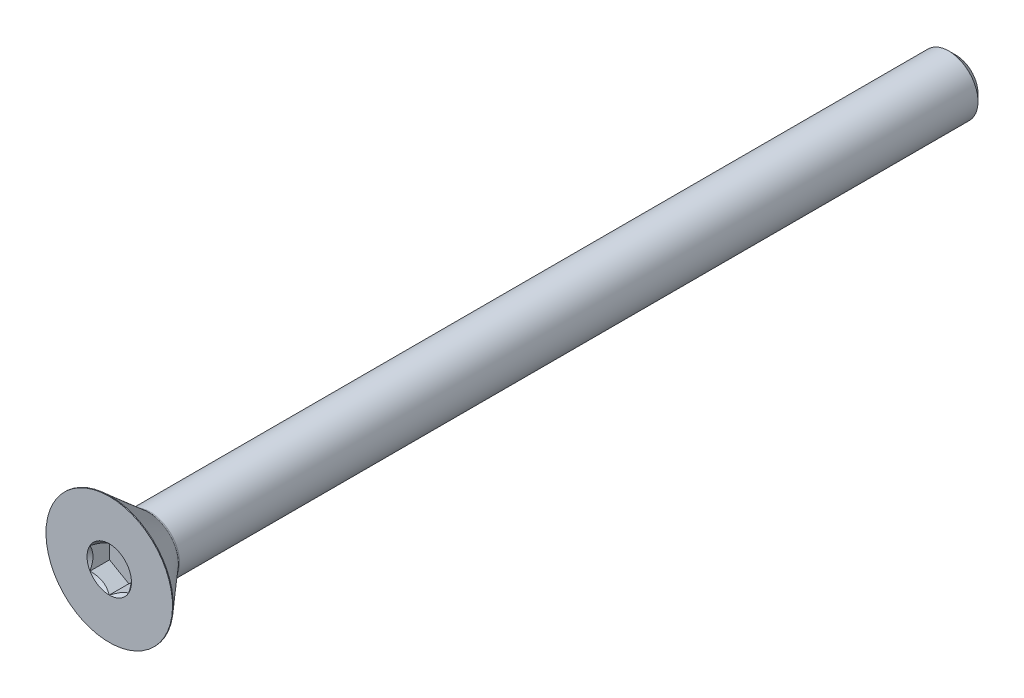
SolidWorks part; units mm, degrees
ref_plane "Front Plane" through (0, 0, 0) normal (0, 0, 1) x (1, 0, 0)
ref_plane "Top Plane" through (0, 0, 0) normal (0, 1, 0) x (1, 0, 0)
ref_plane "Right Plane" through (0, 0, 0) normal (1, 0, 0) x (0, 0, -1)
sketch "Sketch1" plane through (0, 0, 0) normal (1, 0, 0) x (0, 0, -1)
  line L0 (-34.925, 0) -> (34.925, 0) construction
  line L1 (-34.925, 0) -> (-34.925, 5.2197)
  line L2 (-34.925, 5.2197) -> (-34.8605, 5.2197)
  line L3 (-34.8605, 5.2197) -> (-31.6992, 2.4716)
  line L4 (-34.8605, -5.2197) -> (-31.6992, -2.4716)
  line L5 (34.925, 0) -> (34.925, 2.413)
  line L6 (34.925, 2.413) -> (-31.6992, 2.413)
  line L7 (34.3297, 2.413) -> (34.925, 1.8177)
  line L8 (34.8754, 2.4989) -> (35.2723, 1.8115) construction
  line L9 (35.2723, 1.8115) -> (35.6691, 2.4989) construction
  line L10 (35.6691, 2.4989) -> (34.8754, 2.4989) construction
  line L11 (34.9002, 2.456) -> (35.6443, 2.456)
  line L12 (35.6443, 2.456) -> (35.3219, 1.8974)
  line L13 (35.3219, 1.8974) -> (35.2227, 1.8974)
  line L14 (35.2227, 1.8974) -> (34.9002, 2.456)
  line L15 (35.2723, 1.8974) -> (35.2723, 1.8115) construction
  line L16 (34.925, 2.413) -> (35.6195, 2.413) construction
  line L17 (35.2723, 2.4989) -> (35.2723, 2.413) construction
  line L18 (34.925, -2.413) -> (-31.6992, -2.413)
  arc A0 (-31.6992, 2.4716) -> (-31.5424, 2.413) centre (-31.5424, 2.6521) ccw
  point P2 (0, 0)
  point P23 (-33.3121, 0)
  point P27 (35.2723, 2.456)
  point P29 (-34.8605, -5.2197)
  point P31 (32.9406, -2.413)
  point P32 (-21.8758, -5.2197)
  point P33 (21.8758, -5.2197)
  point P34 (-23.1807, -5.2197)
  dimension "Length" = 69.85
  dimension "Head Height" = 3.2258
  dimension "Head Diameter" = 10.4394
  dimension "Countersink Angle" = 82
  dimension "Thread Diameter" = 4.826
  dimension "D2" = 0.0645
  dimension "Pitch" = 0.7937
  dimension "D4" = 0.0992
  dimension "D3" = 45
  dimension "D5" = 0.5953
  dimension "D6" = 1.6129
  dimension "D1" = 1.9844
  dimension "D7" = 13.0492
  dimension "D8" = 13.0493
  dimension "D9" = 11.7443
sketch "Sketch8" plane through (0, 0, 0) normal (0, 0, 1) x (1, 0, 0)
  line L1 (0, 1.8331) -> (-1.5875, 0.9165)
  line L2 (-1.5875, 0.9165) -> (-1.5875, -0.9165)
  line L3 (-1.5875, -0.9165) -> (0, -1.8331)
  line L4 (0, -1.8331) -> (1.5875, -0.9165)
  line L5 (1.5875, -0.9165) -> (1.5875, 0.9165)
  line L6 (1.5875, 0.9165) -> (0, 1.8331)
  circle A0 centre (0, 0) radius 1.5875 construction
  dimension "Drive Size" = 3.175
sketch "Sketch2" plane through (0, 0, 0) normal (1, 0, 0) x (0, 0, -1)
  line L0 (-34.8605, 5.2197) -> (-31.6992, 2.4716) construction
  line L1 (-34.925, 0) -> (-34.925, 5.2197) construction
  line L2 (-34.8605, 5.2197) -> (-31.6992, 2.4716)
  line L3 (-34.925, 0) -> (-34.925, 5.2197)
  line L4 (-34.925, 5.2197) -> (-34.8605, 5.2197) construction
  line L5 (-34.925, 5.2197) -> (-34.8605, 5.2197)
  line L6 (-31.5424, 2.413) -> (34.3297, 2.413)
  line L7 (34.3297, 2.413) -> (34.925, 1.8177)
  line L8 (34.925, 1.8177) -> (34.925, 0)
  line L9 (34.925, 0) -> (-34.925, 0)
  arc A0 (-31.6992, 2.4716) -> (-31.5424, 2.413) centre (-31.5424, 2.6521) ccw construction
  arc A1 (-31.6992, 2.4716) -> (-31.5424, 2.413) centre (-31.5424, 2.6521) ccw
revolve "Revolve1" add sketch "Sketch2" angle 360 about L9
sketch "Sketch9" plane through (0, 0, 34.925) normal (0, 0, 1) x (1, 0, 0)
  line L0 (1.5875, -0.9165) -> (1.5875, 0.9165) construction
  line L1 (0, -1.8331) -> (1.5875, -0.9165) construction
  line L2 (-1.5875, -0.9165) -> (0, -1.8331) construction
  line L3 (-1.5875, 0.9165) -> (-1.5875, -0.9165) construction
  line L4 (0, 1.8331) -> (-1.5875, 0.9165) construction
  line L5 (1.5875, 0.9165) -> (0, 1.8331) construction
  line L6 (1.5875, -0.9165) -> (1.5875, 0.9165)
  line L7 (0, -1.8331) -> (1.5875, -0.9165)
  line L8 (-1.5875, -0.9165) -> (0, -1.8331)
  line L9 (-1.5875, 0.9165) -> (-1.5875, -0.9165)
  line L10 (0, 1.8331) -> (-1.5875, 0.9165)
  line L11 (1.5875, 0.9165) -> (0, 1.8331)
sketch "Sketch10" plane through (0, 0, 34.925) normal (0, 0, 1) x (1, 0, 0)
  circle A0 centre (0, 0) radius 1.8331
extrude "Cut-Extrude2" cut sketch "Sketch10" against normal up to vertex (1.6129 mm away) draft 45 up to point (0, 0, 33.3121)
extrude "Cut-Extrude1" cut sketch "Sketch9" against normal up to vertex (1.6129 mm away) up to point (0, 0, 33.3121)
ref_plane "Plane1" [suppressed] through (0, 0, 31.5424) normal (0, 0, 1) x (1, 0, 0)
split "Split1" [suppressed] bodies to split 111
sketch "Sketch3" [suppressed] plane through (0, 0, -34.925) normal (0, 0, -1) x (-1, 0, 0)
  circle A0 centre (0, 0) radius 2.413 construction
  circle A1 centre (0, 0) radius 2.413
curve "Helix/Spiral1" [suppressed] pitch 0.7937 height 69.85 turns 88
sketch "Sketch4" [suppressed] plane through (0, 0, 0) normal (1, 0, 0) x (0, 0, -1)
  line L0 (34.9002, 2.456) -> (35.6443, 2.456) construction
  line L1 (35.2227, 1.8974) -> (34.9002, 2.456) construction
  line L2 (35.3219, 1.8974) -> (35.2227, 1.8974) construction
  line L3 (35.6443, 2.456) -> (35.3219, 1.8974) construction
  line L4 (34.9002, 2.456) -> (35.6443, 2.456)
  line L5 (35.2227, 1.8974) -> (34.9002, 2.456)
  line L6 (35.3219, 1.8974) -> (35.2227, 1.8974)
  line L7 (35.6443, 2.456) -> (35.3219, 1.8974)
sweep "Cut-Sweep3" [suppressed] cut profiles "Sketch4" path "Helix/Spiral1"
sketch "Sketch11" [suppressed] plane through (0, 0, 31.5424) normal (0, 0, 1) x (1, 0, 0)
  circle A0 centre (0, 0) radius 2.413
extrude "Boss-Extrude1" [suppressed] add sketch "Sketch11" against normal up to next draft 20
equation "\"D2@Sketch1\"=\"Head Height@Sketch1\"/50"
equation "\"D4@Sketch1\" = \"Pitch@Sketch1\" / 8"
equation "\"D5@Sketch1\"=\"Pitch@Sketch1\"*0.75"
equation "\"D4@Helix/Spiral1\"=\"Pitch@Sketch1\""
equation "\"D3@Helix/Spiral1\"=\"Length@Sketch1\""
equation "\"D6@Sketch1\"=\"Head Height@Sketch1\"/2"
equation "\"D1@Sketch1\"=\"Pitch@Sketch1\"*2.5"
equation "\"D7@Sketch1\"=\"Head Diameter@Sketch1\"*1.25"
equation "\"D8@Sketch1\"=\"D7@Sketch1\""
equation "\"D9@Sketch1\"=\"Head Diameter@Sketch1\"*1.125"
